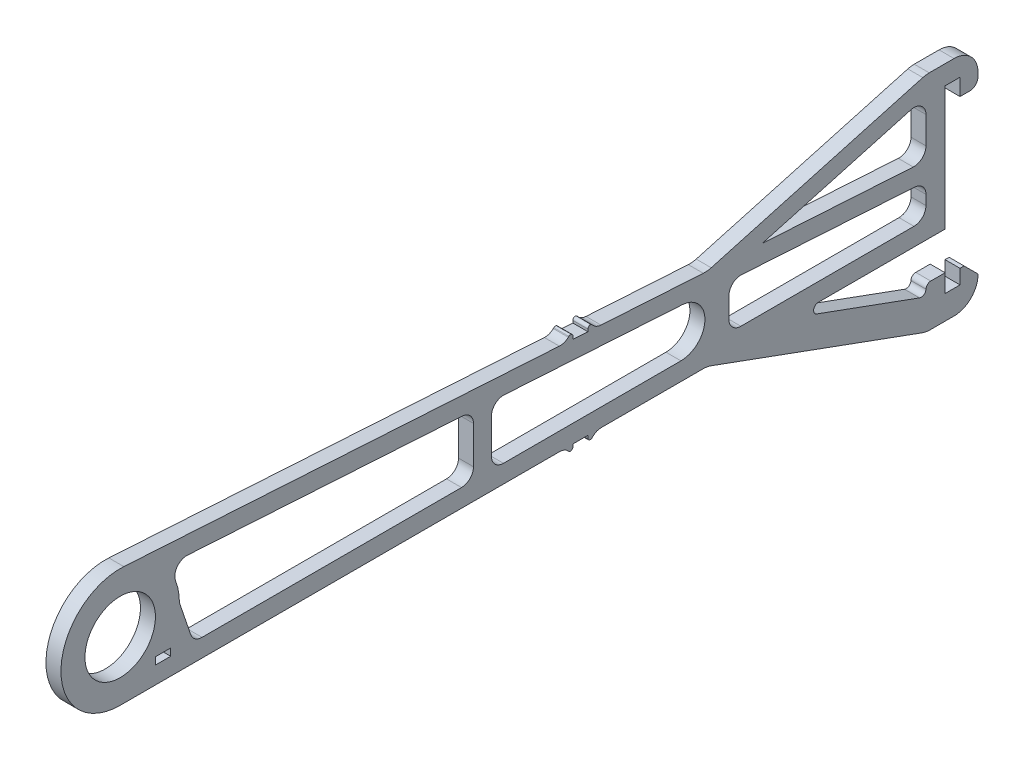
SolidWorks part; units mm, degrees
material "Delrin"
ref_plane "Front Plane" through (0, 0, 0) normal (0, 0, 1) x (1, 0, 0)
ref_plane "Top Plane" through (0, 0, 0) normal (0, 1, 0) x (1, 0, 0)
ref_plane "Right Plane" through (0, 0, 0) normal (1, 0, 0) x (0, 0, -1)
sketch "Sketch1" plane through (0, 0, 0) normal (1, 0, 0) x (0, 0, -1)
  line L0 (0.3859, 6.2619) -> (62.1851, 2.453)
  line L1 (0, -6.2738) -> (62.1851, -6.2738)
  line L2 (85.344, 8.8996) -> (88.3158, 8.8996)
  line L3 (4.7629, 4.0835) -> (85.344, -0.883)
  line L4 (4.5027, -4.3688) -> (85.344, -4.3688)
  line L5 (4.101, 4.1243) -> (87.7175, -1.0293) construction
  line L6 (0, -4.3688) -> (85.344, -4.3688) construction
  line L7 (85.344, -6.2738) -> (85.344, 8.8996) construction
  line L16 (6.2738, 0) -> (7.7597, -4.3688)
  line L17 (39.3251, 1.9533) -> (39.3251, -4.3688)
  line L18 (37.4201, 2.0707) -> (37.4201, -4.3688)
  line L23 (4.2182, 6.0257) -> (87.8347, 0.8721) construction
  line L24 (89.9668, 5.0896) -> (88.9508, 5.0896)
  line L25 (88.9508, 5.0896) -> (88.9508, 6.8676)
  line L26 (88.9508, 6.8676) -> (87.376, 6.8676)
  line L27 (87.376, 6.8676) -> (87.376, -6.2738)
  line L28 (87.376, -12.1824) -> (88.9508, -12.1824)
  line L29 (88.9508, -12.1824) -> (88.9508, -10.6584)
  line L30 (88.9508, -10.6584) -> (89.3826, -10.6584)
  line L31 (90.8558, -12.1316) -> (90.8558, -12.1824)
  line L32 (88.3158, -14.7224) -> (85.344, -14.7224)
  line L33 (85.344, -14.7224) -> (85.344, -6.2738) construction
  line L34 (90.8558, 5.9786) -> (90.8558, 6.3596)
  line L35 (89.3826, -10.6584) -> (90.8558, -12.1316)
  line L36 (64.4711, 0.4035) -> (64.4711, -4.3688)
  line L37 (62.1851, 0.5444) -> (62.1851, -4.3688)
  line L38 (62.1851, 2.453) -> (85.344, 8.8996)
  line L39 (68.0011, 2.0945) -> (85.344, 6.9222)
  line L40 (62.1851, -6.2738) -> (85.344, -14.7224)
  line L41 (71.0788, -6.2738) -> (85.344, -11.4779)
  line L42 (63.2297, -3.4104) -> (86.3886, -11.859) construction
  line L43 (62.696, 0.6178) -> (85.8549, 7.0644) construction
  line L44 (71.0788, -6.2738) -> (85.344, -6.2738)
  line L45 (0, -6.2738) -> (85.344, -6.2738) construction
  line L46 (68.0011, 2.0945) -> (85.344, 1.0256)
  line L47 (62.1851, -4.3688) -> (62.1851, 49995.6312) construction
  line L48 (85.344, 6.9222) -> (85.344, 1.0256)
  line L49 (85.344, -0.883) -> (85.344, -4.3688)
  line L50 (87.376, -12.1824) -> (87.376, -10.2774)
  line L51 (85.344, -6.2738) -> (87.376, -6.2738)
  line L52 (87.376, -10.2774) -> (85.344, -10.2774)
  line L53 (85.344, -10.2774) -> (85.344, -11.4779)
  circle A0 centre (0, 0) radius 3.7338
  circle A1 centre (0, 0) radius 6.2738
  arc A2 (88.3158, 8.8996) -> (90.8558, 6.3596) centre (88.3158, 6.3596) cw
  arc A3 (90.8558, -12.1824) -> (88.3158, -14.7224) centre (88.3158, -12.1824) cw
  arc A4 (90.8558, 5.9786) -> (89.9668, 5.0896) centre (89.9668, 5.9786) cw
  point P47 (90.8558, 8.8996)
  point P50 (90.8558, -14.7224)
  point P53 (90.8558, 5.0896)
  point P54 (90.8558, -10.6584)
  point P56 (90.8558, -10.6584)
  dimension "D1" = 7.4676
  dimension "D2" = 2.54
  dimension "D3" = 5.842
  dimension "D8" = 1.5748
  dimension "D18" = 2.54
  dimension "D19" = 2.54
  dimension "D20" = 0.889
  dimension "D21" = 22.86
  dimension "D5" = 37.4201
  dimension "D10" = 1.905
  dimension "D11" = 1.778
  dimension "D12" = 1.905
  dimension "D4" = 5.3842
  dimension "D9" = 1.5748
  dimension "D14" = 1.524
  dimension "D15" = 3.81
  dimension "D16" = 4.064
  dimension "D17" = 1.905
  dimension "D22" = 19.05
  dimension "D23" = 85.344
  dimension "D24" = 2.032
  dimension "D25" = 2.286
  dimension "D29" = 1.905
  dimension "D6" = 1.905
  dimension "D7" = 1.905
  dimension "D27" = 3.048
  dimension "D28" = 1.905
extrude "Boss-Extrude1" add sketch "Sketch1" along normal blind 1.5875 contours A1 L1 | A1 L4 L16 | L3 L18 L4 L17 | L31 L30 L29 L28 L27 L26 L25 L24 A4 L34 A2 L2 L7 L33 L32 A3 | A1 A0 | L3 L37 L4 L36 region at (0, 3.4205, -31.2278) region at (0, 5.4578, -2.7163) region at (0, -1.1783, -38.3697) region at (0, -3.082, -6.3381) region at (0, -1.9473, -63.3226)
fillet "Fillet1" radius 2.54 4 edges at (0.7937, 2.453, -62.1851) (0.7937, 8.8996, -85.344) (0.7937, -6.2738, -62.1851) (0.7937, -14.7224, -85.344)
fillet "Fillet2" radius 1.27 12 edges at (0.7937, 4.0835, -4.7629) (0.7937, -4.3688, -7.7597) (0.7937, -4.3688, -37.4201) (0.7937, 2.0707, -37.4201) (0.7937, -4.3688, -39.3251) (0.7937, 1.9533, -39.3251) (0.7937, 0.4035, -64.4711) (0.7937, -4.3688, -64.4711) (0.7937, 1.0256, -85.344) (0.7937, 6.9222, -85.344) (0.7937, -0.883, -85.344) (0.7937, -4.3688, -85.344)
fillet "Fillet3" radius 0.508 2 edges at (0.7937, -6.2738, -71.0788) (0.7937, -11.4779, -85.344)
fillet "Fillet4" radius 0.508 1 edges at (0.7937, -10.2774, -85.344)
sketch "Sketch4" plane through (1.5875, 0, 0) normal (1, 0, 0) x (0, 0, -1)
  line L0 (40.6732, 1.8702) -> (62.1851, 0.5444) construction
  line L1 (62.1851, 0.5444) -> (62.1851, -4.3688) construction
  line L2 (40.5951, -4.3688) -> (62.1851, -4.3688) construction
  line L3 (59.5471, 0.707) -> (62.1851, 0.5444)
  line L4 (62.1851, 0.5444) -> (62.1851, -4.3688)
  line L5 (59.3908, -4.3688) -> (62.1851, -4.3688)
  line L6 (61.9311, -1.8285) -> (62.1851, -1.8285) construction
  line L7 (87.376, 6.8676) -> (87.376, -6.2738) construction
  line L8 (40.5951, -4.3688) -> (62.1851, -4.3688) construction
  arc A0 (59.5471, 0.707) -> (59.3908, -4.3688) centre (59.3908, -1.8285) cw
  dimension "D1" = 0.254
extrude "Boss-Extrude2" add sketch "Sketch4" against normal up to surface (1.5875 mm away) up to face at (0, -0.6692, -20.2932)
sketch "Sketch5" plane through (1.5875, 0, 0) normal (1, 0, 0) x (0, 0, -1)
  line L4 (3.7592, -3.683) -> (3.7592, -4.445)
  line L5 (5.3467, -3.683) -> (3.7592, -3.683)
  line L6 (5.3467, -4.445) -> (5.3467, -3.683)
  line L7 (5.3467, -3.683) -> (3.7592, -3.683)
  line L8 (3.7592, -3.683) -> (3.7592, -4.445)
  line L9 (3.7592, -4.445) -> (5.3467, -4.445)
  line L10 (5.3467, -4.445) -> (5.3467, -3.683)
  line L11 (3.7592, -4.445) -> (5.3467, -4.445)
  dimension "D1" = 0
extrude "Cut-Extrude1" cut sketch "Sketch5" against normal up to next
sketch "Sketch6" plane through (0, 0, 0) normal (-1, 0, 0) x (0, 0, 1)
  line L0 (-47.0577, -6.2738) -> (-47.9467, -7.1628)
  line L1 (0, -6.2738) -> (-61.7363, -6.2738) construction
  line L2 (-47.9467, -17.1193) -> (-47.9467, 10.2613) construction
  line L3 (-47.9467, -7.1628) -> (-47.9467, -6.2738)
  line L4 (-47.9467, -6.2738) -> (-47.0577, -6.2738)
  line L5 (-47.0577, -6.2738) -> (-47.0715, -6.2496)
  line L6 (-48.7404, -10.0838) -> (-48.7404, 6.4573) construction
  line L7 (-49.5342, -10.0838) -> (-47.9467, -10.0838) construction
  line L8 (-49.5342, -6.2738) -> (-50.4232, -6.2738)
  line L9 (-49.5342, -7.1628) -> (-49.5342, -6.2738)
  line L10 (-50.4232, -6.2738) -> (-49.5342, -7.1628)
  line L11 (-50.4215, 3.178) -> (-49.5342, 4.1217)
  line L12 (-0.3859, 6.2619) -> (-61.759, 2.4793) construction
  line L13 (-49.5342, -17.1193) -> (-49.5342, 10.2613) construction
  line L14 (-49.5342, 4.1217) -> (-49.5342, 3.2327)
  line L15 (-49.5342, 3.2327) -> (-50.4215, 3.178)
  line L16 (-47.9467, 3.3306) -> (-47.0594, 3.3853)
  line L17 (-47.0594, 3.3853) -> (-47.9467, 4.2196)
  line L18 (-47.9467, 4.2196) -> (-47.9467, 3.3306)
  dimension "D1" = 0.889
extrude "Boss-Extrude3" add sketch "Sketch6" against normal up to surface (1.5875 mm away) contours L4 L3 L0 | L8 L10 L9 | L15 L14 L11 | L17 L18 L16 region at (0, -6.5701, -47.6504) region at (0, -6.5701, -49.8305) region at (0, 3.5108, -49.83) region at (0, 3.6451, -47.6509) up to face at (1.5875, -4.064, -4.553)
fillet "Fillet5" radius 1.27 4 edges at (0.7937, 3.178, -50.4215) (0.7937, 3.3853, -47.0594) (0.7937, -6.2738, -50.4232) (0.7937, -6.2738, -47.0577)
fillet "Fillet6" radius 0.254 4 edges at (0.7937, -7.1628, -49.5342) (0.7937, -7.1628, -47.9467) (0.7937, 4.2196, -47.9467) (0.7937, 4.1217, -49.5342)
